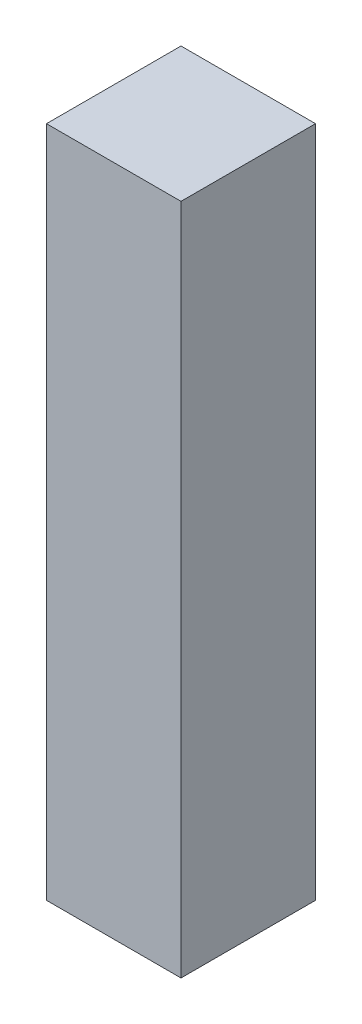
SolidWorks part; units mm, degrees
material "AISI 4340 Acero recocido"
ref_plane "Alzado" through (0, 0, 0) normal (0, 0, 1) x (1, 0, 0)
ref_plane "Planta" through (0, 0, 0) normal (0, 1, 0) x (1, 0, 0)
ref_plane "Vista lateral" through (0, 0, 0) normal (1, 0, 0) x (0, 0, -1)
sketch "Croquis1" plane through (0, 0, 0) normal (0, 1, 0) x (1, 0, 0)
  line L1 (-500, -500) -> (500, -500)
  line L2 (-500, -500) -> (-500, 500)
  line L3 (-500, 500) -> (500, 500)
  line L4 (500, -500) -> (500, 500)
  line L5 (-500, -500) -> (500, 500) construction
  line L6 (-500, 500) -> (500, -500) construction
  point P0 (0, 0)
  dimension "D1" = 1000
  dimension "D2" = 1000
extrude "Saliente-Extruir1" add sketch "Croquis1" along normal blind 5000
ref_point "Punto2"
ref_axis "Eje3" through (0, 5000, 0) along (0, -1, 0)
